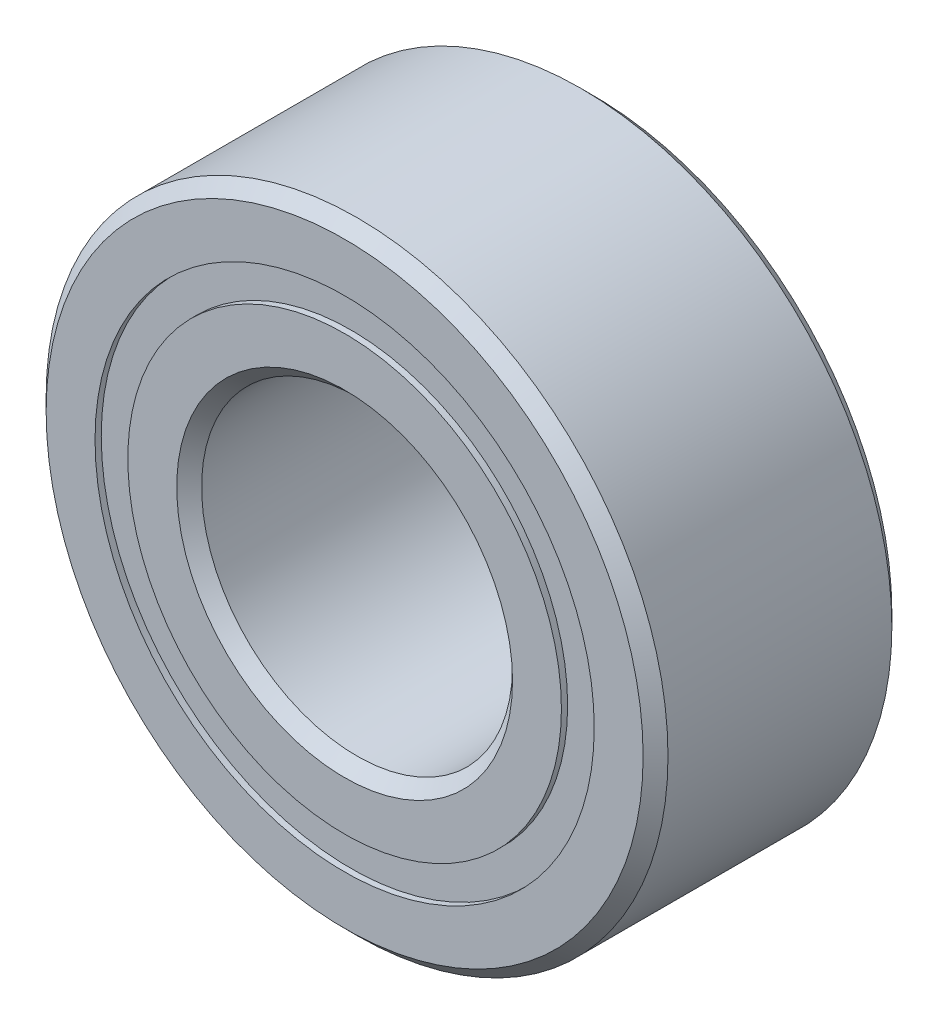
SolidWorks part; units mm, degrees
ref_plane "Front Plane" through (0, 0, 0) normal (0, 0, 1) x (1, 0, 0)
ref_plane "Top Plane" through (0, 0, 0) normal (0, 1, 0) x (1, 0, 0)
ref_plane "Right Plane" through (0, 0, 0) normal (1, 0, 0) x (0, 0, -1)
sketch "Sketch1" plane through (0, 0, 0) normal (1, 0, 0) x (0, 0, -1)
  line L0 (-2, 0) -> (2, 0) construction
  line L1 (0, 5) -> (0, -5) construction
  line L2 (1.8, 5) -> (-1.8, 5)
  line L3 (-1.8, 5) -> (-2, 4.8)
  line L4 (-2, 4.8) -> (-2, 4.0137)
  line L5 (-2, 4.0137) -> (-0.8889, 4.0137)
  line L6 (2, 4.0137) -> (0.8889, 4.0137)
  line L7 (2, 4.8) -> (2, 4.0137)
  line L8 (1.8, 5) -> (2, 4.8)
  line L9 (0, 5) -> (0, 3.75) construction
  line L10 (0, 3.75) -> (0, 2.5) construction
  arc A0 (-0.8889, 4.0137) -> (0.8889, 4.0137) centre (0, 3.75) cw
  point P14 (0, 2.5)
  dimension "Width" = 4
  dimension "OD" = 10
  dimension "D1" = 45
  dimension "D2" = 0.2
  dimension "Shaft Dia" = 5
  dimension "D3" = 1.7778
  dimension "D4" = 0.2637
revolve "Revolve1" add sketch "Sketch1" angle 360 about L0
sketch "Sketch3" plane through (0, 0, 0) normal (1, 0, 0) x (0, 0, -1)
  line L0 (-2, 3.4863) -> (-0.8889, 3.4863)
  line L1 (0, 5) -> (0, -5) construction
  line L2 (-2, 4.8) -> (-2, 4.0137) construction
  line L3 (-2, 3.4863) -> (-2, 2.7)
  line L4 (-1.8, 5) -> (-2, 4.8) construction
  line L5 (-2, 2.7) -> (-1.8, 2.5)
  line L6 (-1.8, 2.5) -> (1.8, 2.5)
  line L7 (1.8, 5) -> (1.8, -5) construction
  line L8 (1.8, 2.5) -> (2, 2.7)
  line L9 (2, -4.8) -> (2, 4.8) construction
  line L10 (2, 2.7) -> (2, 3.4863)
  line L11 (2, 3.4863) -> (0.8889, 3.4863)
  line L13 (1.8, 5) -> (2, 4.8) construction
  arc A0 (0.8889, 4.0137) -> (-0.8889, 4.0137) centre (0, 3.75) ccw construction
  arc A1 (0.8889, 3.4863) -> (-0.8889, 3.4863) centre (0, 3.75) cw
revolve "Revolve3" add sketch "Sketch3" angle 360 about L0
sketch "Sketch4" plane through (0, 0, 0) normal (1, 0, 0) x (0, 0, -1)
  line L0 (-0.9272, 3.75) -> (0.9272, 3.75)
  arc A2 (-0.9272, 3.75) -> (0.9272, 3.75) centre (0, 3.75) cw
  arc A3 (0.8889, 4.0137) -> (-0.8889, 4.0137) centre (0, 3.75) ccw construction
revolve "Revolve4" add sketch "Sketch4" angle 360 about L0
ref_axis "Axis1" through (0, 0, -2) along (0, 0, 1)
pattern_circular "CirPattern1" count 12 every 30 about axis through (0, 0, -2) along (0, 0, 1) of bodies 104
sketch "Sketch5" plane through (0, 0, 0) normal (1, 0, 0) x (0, 0, -1)
  line L0 (-2, 4.0137) -> (-0.8889, 4.0137) construction
  line L1 (-1.9, 4.0137) -> (-0.9272, 4.0137)
  line L2 (-1.9, 4.0137) -> (-1.9, 3.4863)
  line L3 (-1.9, 3.4863) -> (-0.9272, 3.4863)
  line L4 (-0.9272, 4.0137) -> (-0.9272, 3.4863)
  line L5 (-2, 3.4863) -> (-0.8889, 3.4863) construction
  line L6 (2, 4.0137) -> (0.8889, 4.0137) construction
  line L7 (1.9, 4.0137) -> (0.9272, 4.0137)
  line L8 (1.9, 4.0137) -> (1.9, 3.4863)
  line L9 (1.9, 3.4863) -> (0.9272, 3.4863)
  line L10 (0.9272, 4.0137) -> (0.9272, 3.4863)
  line L11 (2, 3.4863) -> (0.8889, 3.4863) construction
  line L12 (-1.8, 5) -> (-2, 4.8) construction
  point P18 (-1.9, 4.9)
revolve "Revolve5" add sketch "Sketch5" angle 360 about L0
sketch "Sketch6" plane through (0, 0, 0) normal (1, 0, 0) x (0, 0, -1)
  line L0 (2, 0) -> (-2, 0) construction
  line L1 (2, 4.0137) -> (0.9, 4.0137)
  line L2 (2, 4.0137) -> (2, 9.5)
  line L3 (2, 9.5) -> (0.9, 9.5)
  line L4 (0.9, 4.0137) -> (0.9, 9.5)
  dimension "Th" = 1.1
  dimension "Flange OD" = 19
revolve "Revolve6" [suppressed] add sketch "Sketch6" angle 360 about L0
equation "\"D2@Sketch1\" = \"Width@Sketch1\"*.05"
equation "\"D3@Sketch1\" = \"Width@Sketch1\"/2.25"
equation "\"D4@Sketch1\" = (((\"OD@Sketch1\"-\"Width@Sketch1\")/2)/3.25)/3.5"
equation "\"D2@CirPattern1\" = 360/\"Balls@CirPattern1\""
